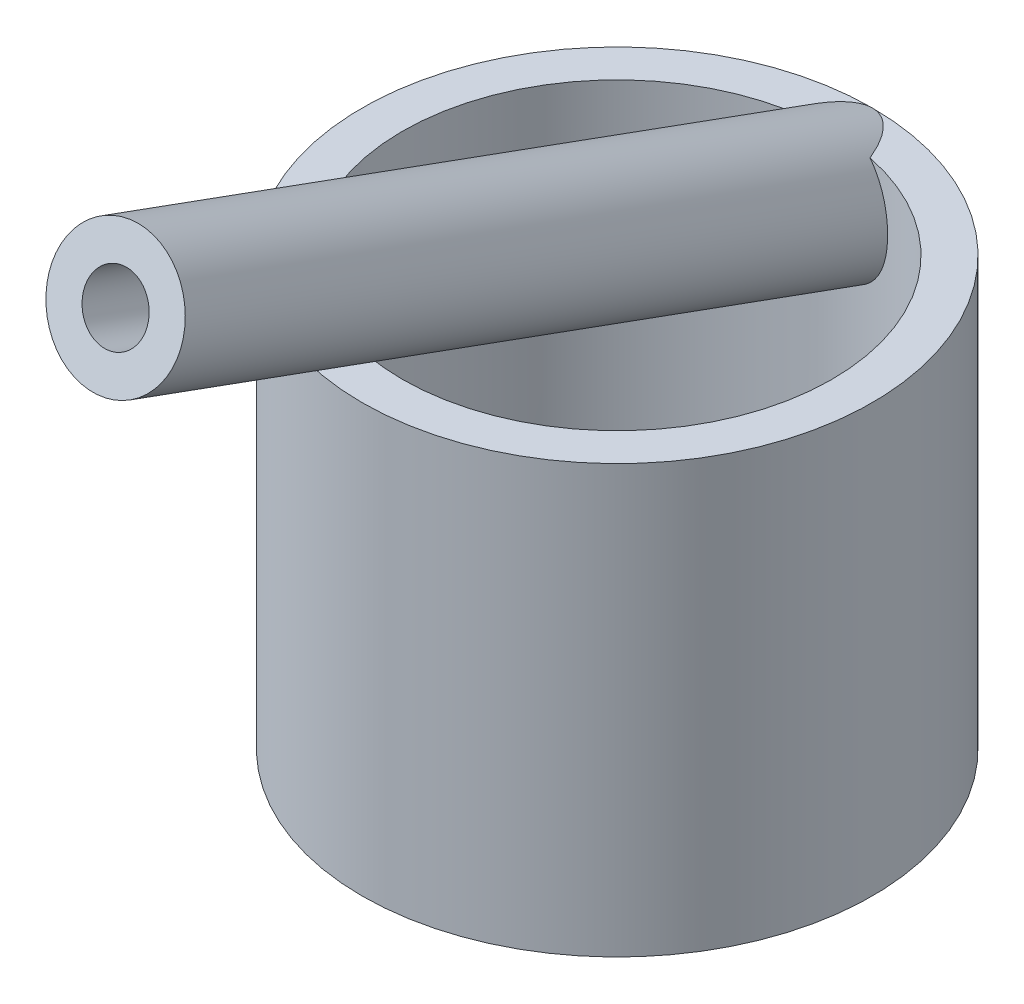
SolidWorks part; units mm, degrees
ref_plane "Front Plane" through (0, 0, 0) normal (0, 0, 1) x (1, 0, 0)
ref_plane "Top Plane" through (0, 0, 0) normal (0, 1, 0) x (1, 0, 0)
ref_plane "Right Plane" through (0, 0, 0) normal (1, 0, 0) x (0, 0, -1)
sketch "Sketch1" plane through (0, 0, 0) normal (0, 1, 0) x (1, 0, 0)
  circle A0 centre (0, 0) radius 11.176
  circle A1 centre (0, 0) radius 13.2715
  dimension "D1" = 22.352
  dimension "D2" = 26.543
extrude "Boss-Extrude1" add sketch "Sketch1" along normal blind 22.225
ref_plane "Plane2" through (0, 0, -13.2715) normal (0, 0, -1) x (-1, 0, 0)
ref_plane "Plane3" through (0, 22.225, 0) normal (0, 1, 0) x (1, 0, 0)
ref_axis "Axis3" through (14.5987, 22.225, -13.2715) along (-1, 0, 0)
ref_plane "Plane4" through (0, -1.6655, -4.5761) normal (0, -0.342, -0.9397) x (-1, 0, 0)
sketch "Sketch2" plane through (0, -1.6655, -4.5761) normal (0, -0.342, -0.9397) x (-1, 0, 0)
  line L1 (-14.5987, 25.4238) -> (14.5987, 25.4238) construction
  circle A0 centre (0, 21.9948) radius 3.429
  circle A1 centre (0, 21.9948) radius 1.651
  ellipse E0 centre (0, 20.8847) end of major axis (13.2715, 20.8847) minor radius 4.5391 construction
  dimension "D1" = 6.858
  dimension "D2" = 3.302
extrude "Boss-Extrude2" add sketch "Sketch2" against normal blind 40.64
